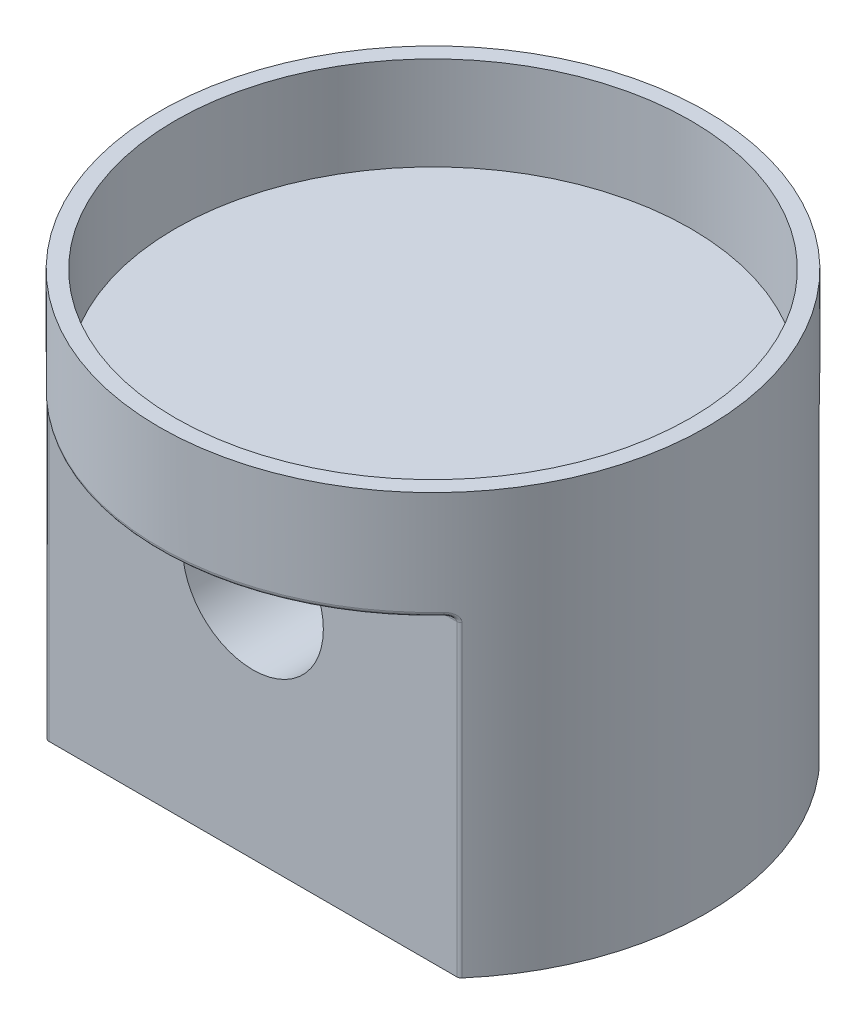
SolidWorks part; units mm, degrees
material "Nylon 101"
ref_plane "Front Plane" through (0, 0, 0) normal (0, 0, 1) x (1, 0, 0)
ref_plane "Top Plane" through (0, 0, 0) normal (0, 1, 0) x (1, 0, 0)
ref_plane "Right Plane" through (0, 0, 0) normal (1, 0, 0) x (0, 0, -1)
sketch "Sketch1" plane through (0, 0, 0) normal (0, 1, 0) x (1, 0, 0)
  circle A0 centre (0, 0) radius 29.25
  dimension "D1" = 58.5
extrude "Boss-Extrude1" add sketch "Sketch1" along normal blind 45
sketch "Sketch2" plane through (0, 45, 0) normal (0, 1, 0) x (1, 0, 0)
  circle A0 centre (0, 0) radius 27.55
  dimension "D1" = 55.1
extrude "Cut-Extrude1" cut sketch "Sketch2" against normal blind 10
sketch "Sketch3" plane through (0, 0, 0) normal (0, 0, 1) x (1, 0, 0)
  circle A0 centre (0, 25.0526) radius 7.525
  dimension "D1" = 15.05
extrude "Cut-Extrude2" cut sketch "Sketch3" against normal through all both and the other way through all
ref_plane "Plane1" through (0, 0, -29.25) normal (0, 0, -1) x (-1, 0, 0)
sketch "Sketch4" plane through (0, 0, -29.25) normal (0, 0, -1) x (-1, 0, 0)
  line L0 (29.25, 0) -> (29.25, 45) construction
  line L1 (-29.25, 0) -> (29.25, 0)
  line L2 (-29.25, 0) -> (-29.25, 33.4)
  line L3 (-29.25, 33.4) -> (29.25, 33.4)
  line L4 (29.25, 0) -> (29.25, 33.4)
  line L5 (29.25, 45) -> (-29.25, 45) construction
  dimension "D1" = 11.6
extrude "Cut-Extrude3" cut sketch "Sketch4" against normal blind 10 and the other way through all
mirror "Mirror1" about plane through (0, 0, 0) normal (0, 0, 1) of "Cut-Extrude3"
fillet "Fillet4" radius 0.5 5 edges at (22.0227, 16.7, -19.25) (-22.0227, 16.7, -19.25) (0, 0, -19.25) (0, 33.4, -19.25) (0, 33.4, -29.25)
fillet "Fillet5" radius 0.5 4 edges at (-22.0227, 16.7, 19.25) (22.0227, 16.7, 19.25) (0, 33.4, 19.25) (0, 33.4, 29.25)
